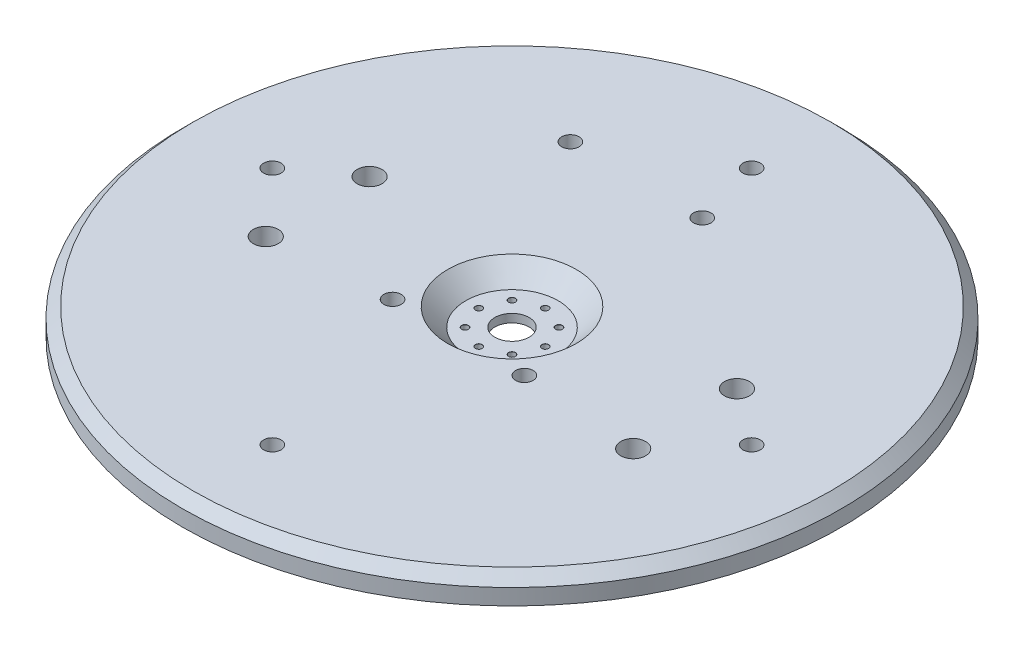
SolidWorks part; units mm, degrees
other "Markup1"
sketch "Sketch21" plane through (-65.5, -15.05, -60) normal (-0.0927, -0.2854, -0.9539) x (0.9951, -0.0609, -0.0785)
material "6061 Alloy"
ref_plane "Front Plane" through (0, 0, 0) normal (0, 0, 1) x (1, 0, 0)
ref_plane "Top Plane" through (0, 0, 0) normal (0, 1, 0) x (1, 0, 0)
ref_plane "Right Plane" through (0, 0, 0) normal (1, 0, 0) x (0, 0, -1)
sketch "Sketch1" plane through (0, 0, 0) normal (0, 1, 0) x (1, 0, 0)
  circle A0 centre (0, 0) radius 79.375
  dimension "D1" = 158.75
extrude "Boss-Extrude1" add sketch "Sketch1" along normal mid plane 6.35
sketch "Sketch2" plane through (0, -3.175, 0) normal (0, -1, 0) x (1, 0, 0)
  circle A0 centre (0, 0) radius 12.065
  circle A1 centre (0, 0) radius 79.375 construction
  dimension "D1" = 24.13
sketch "Sketch5" plane through (0, 3.175, 0) normal (0, 1, 0) x (1, 0, 0)
  circle A0 centre (0, 0) radius 10.4
  circle A1 centre (0, 0) radius 79.375 construction
  dimension "D1" = 20.8
hole_wizard "Tap Drill for M5x0.8 Tap1" positions "Sketch22" profile "Sketch23" hole size "M5x0.8" standard "ANSI Metric" end condition through all
sketch "Sketch22" plane through (0, 3.175, 0) normal (0, 1, 0) x (1, 0, 0)
  point P0 (-27.3188, 41.3898)
  point P3 (4.4312, 41.3898)
  point P6 (-15.875, -12.8959)
  point P9 (15.875, -12.8959)
  dimension "D1" = 31.75
  dimension "D2" = 41.3898
  dimension "D3" = 4.4312
  dimension "D4" = 31.75
  dimension "D5" = 12.8959
  dimension "D6" = 15.875
sketch "Sketch23" plane through (-27.3188, 3.175, -41.3898) normal (1, 0, 0) x (0, 0, 1)
  line L0 (0, 0) -> (0, 6.35)
  line L1 (0, 6.35) -> (2.1, 6.35)
  line L2 (2.1, 6.35) -> (2.1, 0)
  line L5 (2.1, 0) -> (0, 0)
  line L11 (0, -6.35) -> (0, 107.95) construction
  dimension "Thru Hole Dia." = 4.2
  dimension "Thru Hole Depth" = 6.35
hole_wizard "Tap Drill for M7x1.0 Tap1" positions "Sketch24" profile "Sketch25" hole size "M7x1.0" standard "ANSI Metric" end condition through all
sketch "Sketch24" plane through (0, 3.175, 0) normal (0, 1, 0) x (1, 0, 0)
  point P0 (-44.245, 9.9416)
  point P3 (-44.245, -15.0584)
  point P6 (44.245, 9.9416)
  point P9 (44.245, -15.0584)
  dimension "D1" = 25
  dimension "D2" = 44.245
  dimension "D3" = 9.9416
  dimension "D4" = 25
  dimension "D5" = 44.245
  dimension "D6" = 15.0584
sketch "Sketch25" plane through (-44.245, 3.175, -9.9416) normal (1, 0, 0) x (0, 0, 1)
  line L0 (0, 0) -> (0, 6.35)
  line L1 (0, 6.35) -> (3, 6.35)
  line L2 (3, 6.35) -> (3, 0)
  line L5 (3, 0) -> (0, 0)
  line L11 (0, -6.35) -> (0, 107.95) construction
  dimension "Thru Hole Dia." = 6
  dimension "Thru Hole Depth" = 6.35
sketch "Sketch28" plane through (0, 3.175, 0) normal (0, 1, 0) x (1, 0, 0)
  circle A0 centre (0, 0) radius 51
  circle A1 centre (35.8572, -36.2665) radius 4.2952
  dimension "D1" = 102
sketch "Sketch31" plane through (0, 3.175, 0) normal (0, 1, 0) x (1, 0, 0)
  line L1 (5.6569, 5.6569) -> (-5.6569, 5.6569) construction
  line L2 (5.6569, 5.6569) -> (5.6569, -5.6569) construction
  line L3 (5.6569, -5.6569) -> (-5.6569, -5.6569) construction
  line L4 (-5.6569, 5.6569) -> (-5.6569, -5.6569) construction
  line L5 (5.6569, 5.6569) -> (-5.6569, -5.6569) construction
  line L6 (5.6569, -5.6569) -> (-5.6569, 5.6569) construction
  line L7 (8, 0) -> (0, 8) construction
  line L8 (8, 0) -> (0, -8) construction
  line L9 (0, -8) -> (-8, 0) construction
  line L10 (0, 8) -> (-8, 0) construction
  line L11 (8, 0) -> (-8, 0) construction
  line L12 (0, -8) -> (0, 8) construction
  circle A0 centre (0, 0) radius 8 construction
  point P0 (0, 0)
  point P8 (0, 0)
  dimension "D1" = 16
sketch "Sketch32" plane through (0, 3.175, 0) normal (0, 1, 0) x (1, 0, 0)
  circle A0 centre (0, 0) radius 11.127
  circle A1 centre (0, 0) radius 4.127
  dimension "D1" = 22.254
  dimension "D2" = 8.254
extrude "Cut-Extrude1" cut sketch "Sketch32" against normal through all contours A1
extrude "Cut-Extrude2" cut sketch "Sketch32<4>" against normal offset from surface (4.35 mm away) 2 up to face at (0, -3.175, 4.127)
sketch "Sketch32<4>" plane through (0, 3.175, 0) normal (0, 1, 0) x (1, 0, 0) same geometry as "Sketch32"
chamfer "Chamfer1" distance 4.35 angle 45 1 edges at (0, 3.175, 11.127)
hole_wizard "Tap Drill for M2x0.4 Tap1" positions "Sketch33" profile "Sketch34" hole size "M2x0.4" standard "ANSI Metric" end condition through all
sketch "Sketch33" plane through (0, -1.175, 0) normal (0, 1, 0) x (1, 0, 0)
  point P0 (-8, 0)
  point P3 (-5.6569, 5.6569)
  point P6 (0, 8)
  point P9 (5.6569, 5.6569)
  point P12 (8, 0)
  point P15 (5.6569, -5.6569)
  point P18 (0, -8)
  point P21 (-5.6569, -5.6569)
sketch "Sketch34" plane through (-8, -1.175, 0) normal (1, 0, 0) x (0, 0, 1)
  line L0 (0, 0) -> (0, 2)
  line L1 (0, 2) -> (0.8, 2)
  line L2 (0.8, 2) -> (0.8, 0.025)
  line L3 (0.8, 0.025) -> (0.825, 0)
  line L5 (0.825, 0) -> (0, 0)
  line L6 (-0.8, 0.025) -> (-0.825, 0) construction
  line L11 (0, -6.35) -> (0, 107.95) construction
  dimension "Thru Hole Dia." = 1.6
  dimension "Thru Hole Depth" = 2
  dimension "Near C'Sink Dia." = 1.65
  dimension "Near C'Sink Angle" = 90
chamfer "Chamfer2" distance 2.5 angle 45 1 edges at (0, 3.175, 79.375)
sketch "Sketch35" plane through (0, -3.175, 0) normal (0, -1, 0) x (1, 0, 0)
  line L0 (0, 57.7234) -> (0, -57.7234) construction
  line L1 (57.7234, 0) -> (-57.7234, 0) construction
  circle A0 centre (0, 0) radius 57.7234
  dimension "D1" = 115.4468
hole_wizard "Tap Drill for M5x0.8 Tap2" positions "Sketch37" profile "Sketch38" hole size "M5x0.8" standard "ANSI Metric" end condition through all
sketch "Sketch37" plane through (0, 3.175, 0) normal (0, 1, 0) x (1, 0, 0)
  point P0 (-57.7234, 0)
  point P3 (0, 57.7234)
  point P6 (57.7234, 0)
  point P9 (0, -57.7234)
sketch "Sketch38" plane through (-57.7234, 3.175, 0) normal (1, 0, 0) x (0, 0, 1)
  line L0 (0, 0) -> (0, 6.35)
  line L1 (0, 6.35) -> (2.1, 6.35)
  line L2 (2.1, 6.35) -> (2.1, 0)
  line L5 (2.1, 0) -> (0, 0)
  line L11 (0, -6.35) -> (0, 107.95) construction
  dimension "Thru Hole Dia." = 4.2
  dimension "Thru Hole Depth" = 6.35
